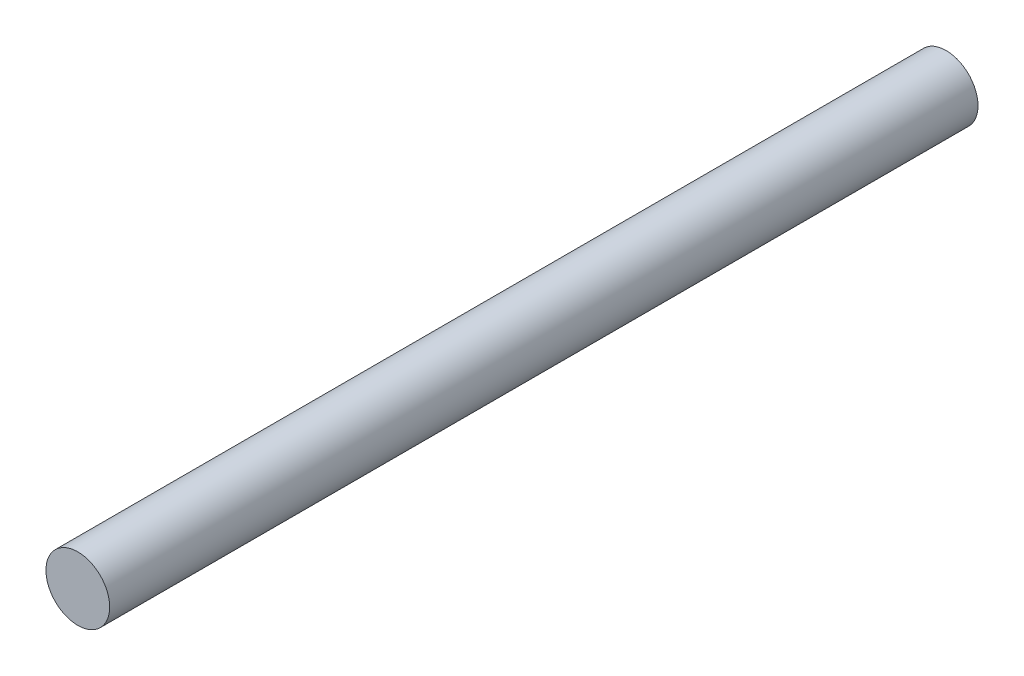
SolidWorks part; units mm, degrees
ref_plane "Alzado" through (0, 0, 0) normal (0, 0, 1) x (1, 0, 0)
ref_plane "Planta" through (0, 0, 0) normal (0, 1, 0) x (1, 0, 0)
ref_plane "Vista lateral" through (0, 0, 0) normal (1, 0, 0) x (0, 0, -1)
sketch "Croquis1" plane through (0, 0, 0) normal (0, 0, 1) x (1, 0, 0)
  circle A0 centre (0, 0) radius 4
  dimension "D1" = 8
extrude "Saliente-Extruir1" add sketch "Croquis1" along normal mid plane 109
ref_plane "Plano2" through (3, 0, 0) normal (1, 0, 0) x (0, 0, -1)
